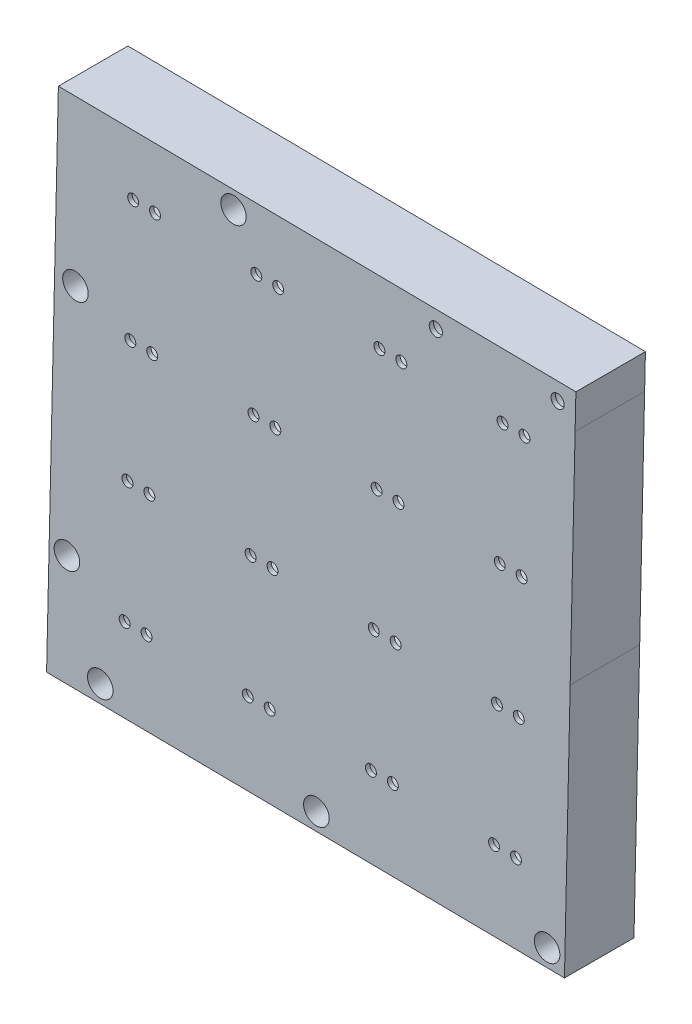
SolidWorks part; units mm, degrees
ref_plane "Front Plane" through (0, 0, 0) normal (0, 0, 1) x (1, 0, 0)
ref_plane "Top Plane" through (0, 0, 0) normal (0, 1, 0) x (1, 0, 0)
ref_plane "Right Plane" through (0, 0, 0) normal (1, 0, 0) x (0, 0, -1)
sketch "Sketch1" plane through (0, 0, 0) normal (0, 0, 1) x (1, 0, 0)
  line L11 (99.4099, -219.1387) -> (-89.6592, -216.966)
  line L12 (-89.6592, -216.966) -> (-93.9705, -404.5237)
  line L13 (-93.9705, -404.5237) -> (95.2285, -406.698)
  line L14 (95.2285, -406.698) -> (99.4099, -219.1387)
  line L21 (95.5208, -393.9822) -> (99.1176, -231.8545)
  line L22 (95.2285, -406.698) -> (95.5208, -393.9822)
  line L23 (-93.9705, -404.5237) -> (95.2285, -406.698)
  line L24 (-89.6592, -216.966) -> (-93.9705, -404.5237)
  line L25 (99.4099, -219.1387) -> (-89.6592, -216.966)
  line L26 (99.1176, -231.8545) -> (99.4099, -219.1387)
  line L27 (95.5208, -393.9822) -> (99.1176, -231.8545)
  line L28 (95.2285, -406.698) -> (95.5208, -393.9822)
  line L29 (-93.9705, -404.5237) -> (95.2285, -406.698)
  line L30 (-89.6592, -216.966) -> (-93.9705, -404.5237)
  line L31 (99.4099, -219.1387) -> (-89.6592, -216.966)
  line L32 (99.1176, -231.8545) -> (99.4099, -219.1387)
  circle A0 centre (80.621, -242.584) radius 2 construction
  circle A1 centre (72.6231, -242.4002) radius 2 construction
  circle A2 centre (35.6329, -241.5499) radius 2 construction
  circle A3 centre (27.635, -241.3661) radius 2 construction
  circle A4 centre (-9.3552, -240.5158) radius 2 construction
  circle A5 centre (-17.3531, -240.3319) radius 2 construction
  circle A6 centre (-54.3434, -239.4817) radius 2 construction
  circle A7 centre (-62.3412, -239.2978) radius 2 construction
  circle A8 centre (-63.3754, -284.2859) radius 2 construction
  circle A9 centre (-55.3775, -284.4698) radius 2 construction
  circle A10 centre (-18.3872, -285.3201) radius 2 construction
  circle A11 centre (-10.3894, -285.5039) radius 2 construction
  circle A12 centre (26.6009, -286.3542) radius 2 construction
  circle A13 centre (34.5988, -286.538) radius 2 construction
  circle A14 centre (71.589, -287.3883) radius 2 construction
  circle A15 centre (79.5869, -287.5721) radius 2 construction
  circle A16 centre (78.5528, -332.5602) radius 2 construction
  circle A17 centre (70.5549, -332.3764) radius 2 construction
  circle A18 centre (33.5646, -331.5261) radius 2 construction
  circle A19 centre (25.5668, -331.3423) radius 2 construction
  circle A20 centre (-11.4235, -330.492) radius 2 construction
  circle A21 centre (-19.4214, -330.3082) radius 2 construction
  circle A22 centre (-56.4116, -329.4579) radius 2 construction
  circle A23 centre (-64.4095, -329.2741) radius 2 construction
  circle A24 centre (-65.4436, -374.2622) radius 2 construction
  circle A25 centre (-57.4457, -374.446) radius 2 construction
  circle A26 centre (-20.4555, -375.2963) radius 2 construction
  circle A27 centre (-12.4576, -375.4801) radius 2 construction
  circle A28 centre (24.5326, -376.3304) radius 2 construction
  circle A29 centre (32.5305, -376.5142) radius 2 construction
  circle A30 centre (69.5208, -377.3645) radius 2 construction
  circle A31 centre (77.5186, -377.5484) radius 2 construction
  circle A32 centre (80.621, -242.584) radius 2
  circle A33 centre (72.6231, -242.4002) radius 2
  circle A34 centre (35.6329, -241.5499) radius 2
  circle A35 centre (27.635, -241.3661) radius 2
  circle A36 centre (-9.3552, -240.5158) radius 2
  circle A37 centre (-17.3531, -240.3319) radius 2
  circle A38 centre (-54.3434, -239.4817) radius 2
  circle A39 centre (-62.3412, -239.2978) radius 2
  circle A40 centre (-63.3754, -284.2859) radius 2
  circle A41 centre (-55.3775, -284.4698) radius 2
  circle A42 centre (-18.3872, -285.3201) radius 2
  circle A43 centre (-10.3894, -285.5039) radius 2
  circle A44 centre (26.6009, -286.3542) radius 2
  circle A45 centre (34.5988, -286.538) radius 2
  circle A46 centre (71.589, -287.3883) radius 2
  circle A47 centre (79.5869, -287.5721) radius 2
  circle A48 centre (78.5528, -332.5602) radius 2
  circle A49 centre (70.5549, -332.3764) radius 2
  circle A50 centre (33.5646, -331.5261) radius 2
  circle A51 centre (25.5668, -331.3423) radius 2
  circle A52 centre (-11.4235, -330.492) radius 2
  circle A53 centre (-19.4214, -330.3082) radius 2
  circle A54 centre (-56.4116, -329.4579) radius 2
  circle A55 centre (-64.4095, -329.2741) radius 2
  circle A56 centre (-65.4436, -374.2622) radius 2
  circle A57 centre (-57.4457, -374.446) radius 2
  circle A58 centre (-20.4555, -375.2963) radius 2
  circle A59 centre (-12.4576, -375.4801) radius 2
  circle A60 centre (24.5326, -376.3304) radius 2
  circle A61 centre (32.5305, -376.5142) radius 2
  circle A62 centre (69.5208, -377.3645) radius 2
  circle A63 centre (77.5186, -377.5484) radius 2
  ellipse E0 centre (-83.4227, -277.0473) end of major axis (-87.0729, -274.0251) minor radius 4.572 construction
  ellipse E1 centre (-25.6726, -224.0609) end of major axis (-30.0759, -225.5071) minor radius 4.572 construction
  ellipse E2 centre (48.2408, -224.9103) end of major axis (49.7468, -226.803) minor radius 2.413 construction
  ellipse E3 centre (92.7302, -225.4215) end of major axis (94.2362, -227.3143) minor radius 2.413 construction
  ellipse E4 centre (88.8809, -400.2655) end of major axis (84.3256, -401.3499) minor radius 4.572 construction
  ellipse E5 centre (4.6064, -399.297) end of major axis (0.0512, -400.3814) minor radius 4.572 construction
  ellipse E6 centre (-86.5415, -363.9079) end of major axis (-91.0967, -364.9923) minor radius 4.572 construction
  ellipse E7 centre (-74.3432, -398.3897) end of major axis (-78.8984, -399.4742) minor radius 4.572 construction
  ellipse E8 centre (-83.4227, -277.0473) end of major axis (-87.0729, -274.0251) minor radius 4.572
  ellipse E9 centre (-25.6726, -224.0609) end of major axis (-30.0759, -225.5071) minor radius 4.572
  ellipse E10 centre (48.2408, -224.9103) end of major axis (49.7468, -226.803) minor radius 2.413
  ellipse E11 centre (92.7302, -225.4215) end of major axis (94.2362, -227.3143) minor radius 2.413
  ellipse E12 centre (88.8809, -400.2655) end of major axis (84.3256, -401.3499) minor radius 4.572
  ellipse E13 centre (4.6064, -399.297) end of major axis (0.0512, -400.3814) minor radius 4.572
  ellipse E14 centre (-86.5415, -363.9079) end of major axis (-91.0967, -364.9923) minor radius 4.572
  ellipse E15 centre (-74.3432, -398.3897) end of major axis (-78.8984, -399.4742) minor radius 4.572
  dimension "D1" = 0
extrude "Boss-Extrude1" add sketch "Sketch1" against normal blind 1.5875 contours L27 L32 L11 L12 L13 L14 E15 E14 E13 E12 E11 E10 E9 E8 A63 A62 A61 A60 A59 A58 A57 A56 A55 A54 A53 A52 A51 A50 region at (2.9991, -311.6009, 0)
ref_plane "Plane1" through (-93.9705, -404.5237, 5) normal (-0.9999, 0.0115, 0) x (0, 0, 1)
ref_plane "Plane2" through (158.3173, -225.775, 115.9625) normal (-0.2101, -0.05, 0.9764) x (0.9777, -0.0108, 0.2099)
sketch "Sketch5" plane through (0, 0, -1.5875) normal (0, 0, -1) x (-1, 0, 0)
  line L0 (65.4436, -374.2622) -> (57.4457, -374.446) construction
  line L1 (65.5351, -378.2437) -> (57.5372, -378.4275)
  line L2 (65.3521, -370.2806) -> (57.3542, -370.4645)
  line L3 (20.4555, -375.2963) -> (12.4576, -375.4801) construction
  line L4 (20.547, -379.2778) -> (12.5491, -379.4617)
  line L5 (20.364, -371.3148) -> (12.3661, -371.4986)
  line L6 (-24.5326, -376.3304) -> (-32.5305, -376.5142) construction
  line L7 (-24.4411, -380.3119) -> (-32.439, -380.4958)
  line L8 (-24.6242, -372.3489) -> (-32.6221, -372.5327)
  line L9 (-69.5208, -377.3645) -> (-77.5186, -377.5484) construction
  line L10 (-69.4292, -381.346) -> (-77.4271, -381.5299)
  line L11 (-69.6123, -373.383) -> (-77.6102, -373.5668)
  line L12 (64.4095, -329.2741) -> (56.4116, -329.4579) construction
  line L13 (64.501, -333.2558) -> (56.5031, -333.4397)
  line L14 (64.3179, -325.2923) -> (56.3201, -325.4761)
  line L15 (19.4214, -330.3082) -> (11.4235, -330.492) construction
  line L16 (19.5129, -334.29) -> (11.515, -334.4738)
  line L17 (19.3298, -326.3264) -> (11.3319, -326.5102)
  line L18 (-25.5668, -331.3423) -> (-33.5646, -331.5261) construction
  line L19 (-25.4752, -335.3238) -> (-33.4731, -335.5077)
  line L20 (-25.6583, -327.3608) -> (-33.6562, -327.5446)
  line L21 (-26.6009, -286.3542) -> (-34.5988, -286.538) construction
  line L22 (-26.5093, -290.336) -> (-34.5072, -290.5198)
  line L23 (-26.6924, -282.3724) -> (-34.6903, -282.5562)
  line L24 (18.3872, -285.3201) -> (10.3894, -285.5039) construction
  line L25 (18.4788, -289.3016) -> (10.4809, -289.4854)
  line L26 (18.2957, -281.3385) -> (10.2978, -281.5224)
  line L27 (-70.5549, -332.3764) -> (-78.5528, -332.5602) construction
  line L28 (-70.4634, -336.3579) -> (-78.4612, -336.5418)
  line L29 (-70.6464, -328.3949) -> (-78.6443, -328.5787)
  line L30 (-71.589, -287.3883) -> (-79.5869, -287.5721) construction
  line L31 (-71.4975, -291.3698) -> (-79.4954, -291.5537)
  line L32 (-71.6805, -283.4068) -> (-79.6784, -283.5906)
  line L33 (-27.635, -241.3661) -> (-35.6329, -241.5499) construction
  line L34 (-27.5435, -245.3476) -> (-35.5414, -245.5314)
  line L35 (-27.7265, -237.3845) -> (-35.7244, -237.5684)
  line L36 (-72.6231, -242.4002) -> (-80.621, -242.584) construction
  line L37 (-72.5316, -246.3817) -> (-80.5295, -246.5655)
  line L38 (-72.7146, -238.4186) -> (-80.7125, -238.6025)
  line L39 (17.3531, -240.3319) -> (9.3552, -240.5158) construction
  line L40 (17.4446, -244.3135) -> (9.4468, -244.4973)
  line L41 (17.2616, -236.3504) -> (9.2637, -236.5343)
  line L42 (62.3412, -239.2978) -> (54.3434, -239.4817) construction
  line L43 (62.4328, -243.2796) -> (54.4349, -243.4635)
  line L44 (62.2497, -235.316) -> (54.2518, -235.4999)
  line L45 (63.3754, -284.2859) -> (55.2887, -284.3271) construction
  line L46 (63.3956, -288.2685) -> (55.309, -288.3096)
  line L47 (63.3551, -280.3034) -> (55.2684, -280.3445)
  line L48 (65.5351, -378.2437) -> (65.3521, -370.2806) construction
  line L49 (20.364, -371.3148) -> (20.547, -379.2778) construction
  line L50 (-24.4411, -380.3119) -> (-24.6242, -372.3489) construction
  line L51 (-69.6123, -373.383) -> (-69.4292, -381.346) construction
  line L52 (-70.4634, -336.3579) -> (-70.6464, -328.3949) construction
  line L53 (-25.4752, -335.3238) -> (-25.6583, -327.3608) construction
  line L54 (19.5129, -334.29) -> (19.4214, -326.3253) construction
  line L55 (64.501, -333.2558) -> (64.4095, -325.2912) construction
  line L56 (63.3956, -288.2685) -> (63.3551, -280.3034) construction
  line L57 (62.4328, -243.2796) -> (62.3412, -235.315) construction
  line L58 (17.4446, -244.3135) -> (17.2616, -236.3504) construction
  line L59 (18.4788, -289.3016) -> (18.2957, -281.3385) construction
  line L60 (-26.5093, -290.336) -> (-26.6009, -282.3713) construction
  line L61 (-27.5435, -245.3476) -> (-27.7265, -237.3845) construction
  line L62 (-71.4975, -291.3698) -> (-71.6805, -283.4068) construction
  line L63 (-72.5316, -246.3817) -> (-72.7146, -238.4186) construction
  line L64 (93.9705, -404.5237) -> (-95.2285, -406.698) construction
  line L65 (89.6592, -216.966) -> (93.9705, -404.5237) construction
  line L66 (-99.4099, -219.1387) -> (89.6592, -216.966) construction
  line L67 (-95.2285, -406.698) -> (-97.3192, -312.9183) construction
  line L68 (-97.3192, -312.9183) -> (-99.1176, -231.8545) construction
  line L69 (-99.1176, -231.8545) -> (-99.4099, -219.1387) construction
  line L70 (93.9705, -404.5237) -> (-95.2285, -406.698)
  line L71 (89.6592, -216.966) -> (93.9705, -404.5237)
  line L72 (-99.4099, -219.1387) -> (89.6592, -216.966)
  line L73 (-95.2285, -406.698) -> (-97.3192, -312.9183)
  line L74 (-97.3192, -312.9183) -> (-99.1176, -231.8545)
  line L75 (-99.1176, -231.8545) -> (-99.4099, -219.1387)
  arc A0 (65.5351, -378.2437) -> (65.3521, -370.2806) centre (65.4436, -374.2622) ccw
  arc A1 (57.3542, -370.4645) -> (57.5372, -378.4275) centre (57.4457, -374.446) ccw
  arc A2 (20.547, -379.2778) -> (20.364, -371.3148) centre (20.4555, -375.2963) ccw
  arc A3 (12.3661, -371.4986) -> (12.5491, -379.4617) centre (12.4576, -375.4801) ccw
  arc A4 (-24.4411, -380.3119) -> (-24.6242, -372.3489) centre (-24.5326, -376.3304) ccw
  arc A5 (-32.6221, -372.5327) -> (-32.439, -380.4958) centre (-32.5305, -376.5142) ccw
  arc A6 (-69.4292, -381.346) -> (-69.6123, -373.383) centre (-69.5208, -377.3645) ccw
  arc A7 (-77.6102, -373.5668) -> (-77.4271, -381.5299) centre (-77.5186, -377.5484) ccw
  arc A8 (64.501, -333.2558) -> (64.3179, -325.2923) centre (64.4095, -329.2741) ccw
  arc A9 (56.3201, -325.4761) -> (56.5031, -333.4397) centre (56.4116, -329.4579) ccw
  arc A10 (19.5129, -334.29) -> (19.3298, -326.3264) centre (19.4214, -330.3082) ccw
  arc A11 (11.3319, -326.5102) -> (11.515, -334.4738) centre (11.4235, -330.492) ccw
  arc A12 (-25.4752, -335.3238) -> (-25.6583, -327.3608) centre (-25.5668, -331.3423) ccw
  arc A13 (-33.6562, -327.5446) -> (-33.4731, -335.5077) centre (-33.5646, -331.5261) ccw
  arc A14 (-26.5093, -290.336) -> (-26.6924, -282.3724) centre (-26.6009, -286.3542) ccw
  arc A15 (-34.6903, -282.5562) -> (-34.5072, -290.5198) centre (-34.5988, -286.538) ccw
  arc A16 (18.4788, -289.3016) -> (18.2957, -281.3385) centre (18.3872, -285.3201) ccw
  arc A17 (10.2978, -281.5224) -> (10.4809, -289.4854) centre (10.3894, -285.5039) ccw
  arc A18 (-70.4634, -336.3579) -> (-70.6464, -328.3949) centre (-70.5549, -332.3764) ccw
  arc A19 (-78.6443, -328.5787) -> (-78.4612, -336.5418) centre (-78.5528, -332.5602) ccw
  arc A20 (-71.4975, -291.3698) -> (-71.6805, -283.4068) centre (-71.589, -287.3883) ccw
  arc A21 (-79.6784, -283.5906) -> (-79.4954, -291.5537) centre (-79.5869, -287.5721) ccw
  arc A22 (-27.5435, -245.3476) -> (-27.7265, -237.3845) centre (-27.635, -241.3661) ccw
  arc A23 (-35.7244, -237.5684) -> (-35.5414, -245.5314) centre (-35.6329, -241.5499) ccw
  arc A24 (-72.5316, -246.3817) -> (-72.7146, -238.4186) centre (-72.6231, -242.4002) ccw
  arc A25 (-80.7125, -238.6025) -> (-80.5295, -246.5655) centre (-80.621, -242.584) ccw
  arc A26 (17.4446, -244.3135) -> (17.2616, -236.3504) centre (17.3531, -240.3319) ccw
  arc A27 (9.2637, -236.5343) -> (9.4468, -244.4973) centre (9.3552, -240.5158) ccw
  arc A28 (62.4328, -243.2796) -> (62.2497, -235.316) centre (62.3412, -239.2978) ccw
  arc A29 (54.2518, -235.4999) -> (54.4349, -243.4635) centre (54.3434, -239.4817) ccw
  arc A30 (63.3956, -288.2685) -> (63.3551, -280.3034) centre (63.3754, -284.2859) ccw
  arc A31 (55.2684, -280.3445) -> (55.309, -288.3096) centre (55.2887, -284.3271) ccw
  circle A32 centre (-92.7302, -225.4215) radius 5.08
  circle A33 centre (-48.2408, -224.9103) radius 5.08
  ellipse E0 centre (-88.8809, -400.2655) end of major axis (-84.3256, -401.3499) minor radius 4.572 construction
  ellipse E1 centre (-4.6064, -399.297) end of major axis (-0.0512, -400.3814) minor radius 4.572 construction
  ellipse E2 centre (74.3432, -398.3897) end of major axis (78.8984, -399.4742) minor radius 4.572 construction
  ellipse E3 centre (86.5415, -363.9079) end of major axis (91.0967, -364.9923) minor radius 4.572 construction
  ellipse E4 centre (83.4227, -277.0473) end of major axis (87.0729, -274.0251) minor radius 4.572 construction
  ellipse E5 centre (25.6726, -224.0609) end of major axis (30.0759, -225.5071) minor radius 4.572 construction
  ellipse E6 centre (-88.8809, -400.2655) end of major axis (-84.3256, -401.3499) minor radius 4.572
  ellipse E7 centre (-4.6064, -399.297) end of major axis (-0.0512, -400.3814) minor radius 4.572
  ellipse E8 centre (74.3432, -398.3897) end of major axis (78.8984, -399.4742) minor radius 4.572
  ellipse E9 centre (86.5415, -363.9079) end of major axis (91.0967, -364.9923) minor radius 4.572
  ellipse E10 centre (83.4227, -277.0473) end of major axis (87.0729, -274.0251) minor radius 4.572
  ellipse E11 centre (25.6726, -224.0609) end of major axis (30.0759, -225.5071) minor radius 4.572
  point P4 (61.4446, -374.3541)
  point P13 (16.4565, -375.3882)
  point P18 (-28.5316, -376.4223)
  point P27 (-73.5197, -377.4564)
  point P36 (60.4105, -329.366)
  point P45 (15.4224, -330.4001)
  point P54 (-29.5657, -331.4342)
  point P63 (-30.5998, -286.4461)
  point P72 (14.3883, -285.412)
  point P83 (-74.5538, -332.4683)
  point P90 (-75.5879, -287.4802)
  point P99 (-31.6339, -241.458)
  point P108 (-76.6221, -242.4921)
  point P117 (13.3542, -240.4239)
  point P126 (58.3423, -239.3897)
  point P135 (59.332, -284.3065)
  dimension "D1" = 10.16
extrude "Boss-Extrude2" add sketch "Sketch5" along normal blind 23.8125
